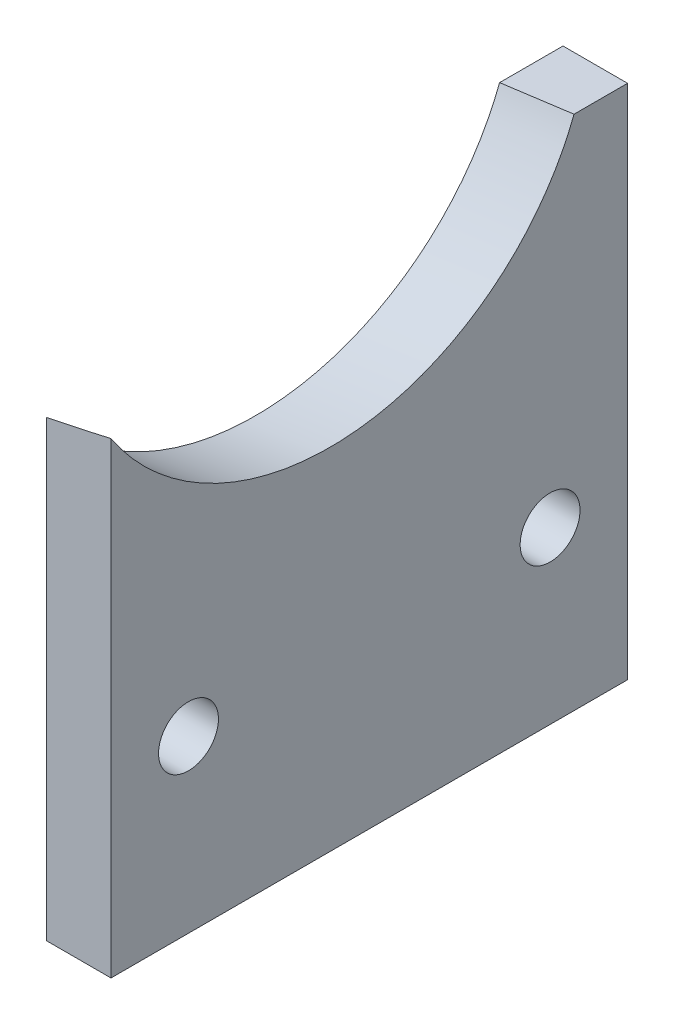
SolidWorks part; units mm, degrees
ref_plane "Front Plane" through (0, 0, 0) normal (0, 0, 1) x (1, 0, 0)
ref_plane "Top Plane" through (0, 0, 0) normal (0, 1, 0) x (1, 0, 0)
ref_plane "Right Plane" through (0, 0, 0) normal (1, 0, 0) x (0, 0, -1)
sketch "Sketch1" plane through (0, 0, 0) normal (1, 0, 0) x (0, 0, -1)
  line L1 (-12.7, -12.7) -> (12.7, -12.7)
  line L2 (-12.7, -12.7) -> (-12.7, 12.7)
  line L4 (12.7, -12.7) -> (12.7, 12.7)
  line L5 (-12.7, -12.7) -> (12.7, 12.7) construction
  line L6 (-12.7, 12.7) -> (12.7, -12.7) construction
  line L7 (-12.7, 12.7) -> (12.7, 12.7)
  point P0 (0, 0)
  dimension "D1" = 25.4
  dimension "D3" = 25.4
extrude "Boss-Extrude1" add sketch "Sketch1" along normal blind 3.175
sketch "Sketch6" plane through (0, 0, 0) normal (-1, 0, 0) x (0, 0, 1)
  circle A0 centre (-8.8899, -4.309) radius 1.4732
  dimension "D1" = 2.9464
extrude "Cut-Extrude2" cut sketch "Sketch6" against normal through all both and the other way through all
mirror "Mirror2" about plane through (0, 0, 0) normal (0, 0, 1) of "Cut-Extrude2"
ref_plane "Plane1" through (-131.2139, 17.2139, 22.4851) normal (-0.9885, 0, 0.1511) x (0.1511, 0, 0.9885)
sketch "Sketch7" plane through (-131.2139, 17.2139, 22.4851) normal (-0.9885, 0, 0.1511) x (0.1511, 0, 0.9885)
  circle A0 centre (0, 0) radius 12.7
  dimension "D1" = 25.4
extrude "Boss-Extrude2" add sketch "Sketch7" against normal blind 2540 separate body
combine bodies "Combine1" operation type subtract main body 107 bodies to subtract 110
